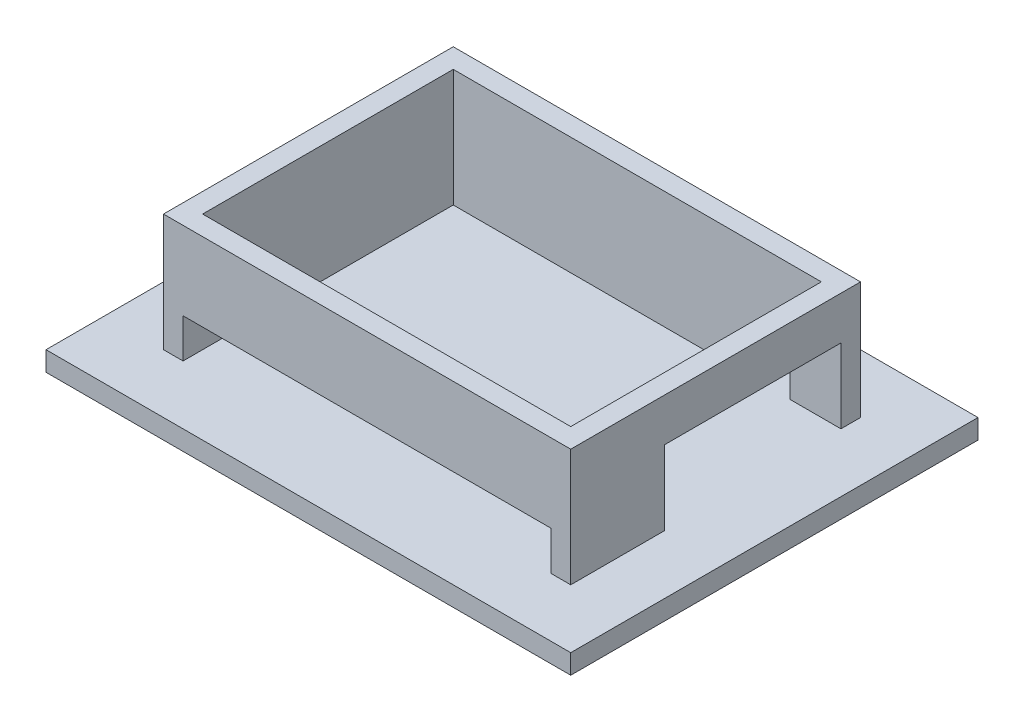
SolidWorks part; units mm, degrees
material "ABS"
ref_plane "Front Plane" through (0, 0, 0) normal (0, 0, 1) x (1, 0, 0)
ref_plane "Top Plane" through (0, 0, 0) normal (0, 1, 0) x (1, 0, 0)
ref_plane "Right Plane" through (0, 0, 0) normal (1, 0, 0) x (0, 0, -1)
sketch "Sketch3" plane through (0, 0, 0) normal (0, 1, 0) x (1, 0, 0)
  line L0 (-67, 52) -> (67, 52)
  line L5 (47, 32) -> (-47, -32) construction
  line L6 (47, -32) -> (-47, 32) construction
  line L7 (47, 32) -> (-47, 32)
  line L8 (47, 32) -> (47, -32)
  line L9 (47, -32) -> (-47, -32)
  line L10 (-47, 32) -> (-47, -32)
  line L11 (47, 32) -> (-47, -32) construction
  line L12 (47, -32) -> (-47, 32) construction
  line L13 (67, 52) -> (67, -52)
  line L14 (67, -52) -> (-67, -52)
  line L15 (-67, -52) -> (-67, 52)
  point P0 (0, 0)
  point P6 (0, 0)
  dimension "D1" = 64
  dimension "D2" = 94
  dimension "D3" = 20
  dimension "D4" = 20
  dimension "D5" = 20
  dimension "D6" = 20
extrude "Boss-Extrude2" add sketch "Sketch3" along normal blind 35 contours L8 L7 L10 L9 | L15 L0 L13 L14
extrude "Boss-Extrude3" add sketch "Sketch3<6>" along normal blind 5 contours L8 L7 L10 L9
sketch "Sketch3<6>" plane through (0, 0, 0) normal (0, 1, 0) x (1, 0, 0) same geometry as "Sketch3"
sketch "Sketch8" plane through (0, 35, 0) normal (0, 1, 0) x (1, 0, 0)
  line L1 (47, 32) -> (-47, 32)
  line L2 (47, 32) -> (47, -32)
  line L3 (47, -32) -> (-47, -32)
  line L4 (-47, 32) -> (-47, -32)
  line L5 (47, 32) -> (-47, -32) construction
  line L6 (47, -32) -> (-47, 32) construction
  line L7 (52, 37) -> (-52, 37)
  line L8 (52, 37) -> (52, -37)
  line L9 (52, -37) -> (-52, -37)
  line L10 (-52, 37) -> (-52, -37)
  line L11 (52, 37) -> (-52, -37) construction
  line L12 (52, -37) -> (-52, 37) construction
  line L17 (67, 52) -> (-67, 52)
  line L18 (67, 52) -> (67, -52)
  line L19 (67, -52) -> (-67, -52)
  line L20 (-67, 52) -> (-67, -52)
  line L21 (67, 52) -> (-67, -52) construction
  line L22 (67, -52) -> (-67, 52) construction
  point P0 (0, 0)
  point P6 (0, 0)
  point P17 (0, 0)
  line M13 (-67, -52) -> (67, -52)
  line M14 (67, -52) -> (67, 52)
  line M15 (67, 52) -> (-67, 52)
  line M16 (-67, 52) -> (-67, -52)
  dimension "D1" = 5
  dimension "D2" = 5
extrude "Cut-Extrude3" cut sketch "Sketch8" against normal offset from surface (30 mm away) 5 contours L10 L7 L8 L9 M16 M13 M14 M15 region at (65.3038, 35, 0) up to face at (0, 0, 0)
sketch "Sketch5" plane through (67, 0, 0) normal (1, 0, 0) x (0, 0, -1)
  line L1 (32, 24) -> (-13, 24)
  line L2 (32, 24) -> (32, 5.263)
  line L3 (32, 5) -> (-13, 5)
  line L4 (-13, 24) -> (-13, 5)
  line L5 (32, 24) -> (-13, 5) construction
  line L6 (32, 5) -> (-13, 24) construction
  line L7 (32, 35) -> (32, 5) construction
  line L9 (32, 35) -> (32, 5)
  line M12 (52, 5) -> (-52, 5)
  dimension "D1" = 19
  dimension "D4" = 45
extrude "Cut-Extrude4" cut sketch "Sketch5" against normal up to surface (114 mm away) contours L9 L2 L1 L4 M12 region at (67, 14.5, -9.5) up to face at (-47, 20, 0)
sketch "Sketch9" plane through (0, 0, 37) normal (0, 0, 1) x (1, 0, 0)
  line L0 (-67, 5) -> (67, 5) construction
  line L1 (-47, 15) -> (47, 15)
  line L2 (-47, 15) -> (-47, 5)
  line L3 (-47, 5) -> (47, 5)
  line L4 (47, 15) -> (47, 5)
  line L5 (52, 5) -> (52, 35) construction
  line L6 (-52, 5) -> (-52, 35) construction
  dimension "D1" = 10
  dimension "D2" = 5
  dimension "D3" = 5
extrude "Cut-Extrude5" cut sketch "Sketch9" against normal blind 5
sketch "Sketch10" plane through (0, 0, -37) normal (0, 0, -1) x (-1, 0, 0)
  line L0 (-52, 5) -> (52, 5) construction
  line L1 (-47, 5) -> (-30, 5)
  line L2 (-47, 5) -> (-47, 15)
  line L3 (-47, 15) -> (-30, 15)
  line L4 (-30, 5) -> (-30, 15)
  line L5 (-52, 5) -> (-52, 35) construction
  dimension "D1" = 17
  dimension "D2" = 10
  dimension "D3" = 5
extrude "Cut-Extrude6" cut sketch "Sketch10" against normal blind 5
sketch "Sketch11" plane through (0, 0, -37) normal (0, 0, -1) x (-1, 0, 0)
  line L0 (-30, 5) -> (52, 5) construction
  line L1 (-48.8247, 17.4323) -> (-19.8414, 17.4323)
  line L2 (-48.8247, 17.4323) -> (-48.8247, 5)
  line L3 (-48.8247, 5) -> (-19.8414, 5)
  line L4 (-19.8414, 17.4323) -> (-19.8414, 5)
extrude "Boss-Extrude4" add sketch "Sketch11" against normal up to surface (5 mm away) up to face at (25.8, 16.8, -32)
sketch "Sketch13" plane through (0, 0, -37) normal (0, 0, -1) x (-1, 0, 0)
  line L0 (-47, 35) -> (-47, 24) construction
  line L1 (-47, 35) -> (-47, 24)
  line L3 (-39, 11) -> (-27, 11)
  line L4 (-52, 5) -> (52, 5)
  line L5 (52, 5) -> (52, 35)
  line L6 (52, 35) -> (-52, 35)
  line L7 (-52, 35) -> (-52, 5)
  line L8 (-52, 5) -> (52, 5)
  line L9 (52, 5) -> (52, 35)
  line L10 (52, 35) -> (-52, 35)
  line L11 (-52, 35) -> (-52, 5)
  line L12 (-39, 11) -> (-39, 5)
  line L13 (-39, 5) -> (-27, 5)
  line L14 (-27, 11) -> (-27, 5)
  dimension "D2" = 8
  dimension "D3" = 12
  dimension "D4" = 6
  dimension "D1" = 0
extrude "Cut-Extrude7" cut sketch "Sketch13" against normal blind 10 contours L14 L3 L12 L8 region at (33, 8, -37)
